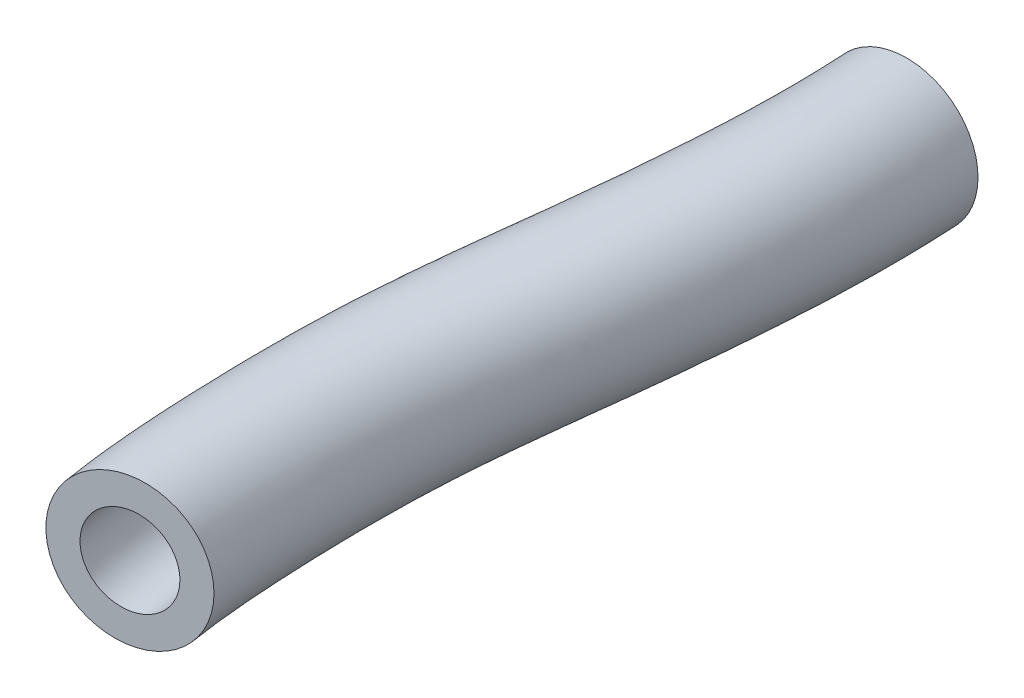
SolidWorks part; units mm, degrees
material "Rubber"
ref_plane "Front Plane" through (0, 0, 0) normal (0, 0, 1) x (1, 0, 0)
ref_plane "Top Plane" through (0, 0, 0) normal (0, 1, 0) x (1, 0, 0)
ref_plane "Right Plane" through (0, 0, 0) normal (1, 0, 0) x (0, 0, -1)
sketch3d "3DSketch1"
  line L0 (-0.2835, -1.1225, 176.7778) -> (-6.8913, -1.6732, 126.4124) construction
  circle A0 centre (0, 0, 24.058) radius 7.5 construction
  circle A1 centre (-6.8913, -1.6732, 126.4124) radius 9.525 construction
  spline S0 degree 3 poles (0, 0, 0) (0.9431, 0.1568, 13.8798) (-2.8576, -0.4693, 64.5894) (-9.8507, -1.7292, 81.5582) (-6.8802, -1.6984, 129.5265) (-5.3863, -1.5478, 137.8842) knots 0 0 0 0 0.211217 0.853755 1 1 1 1
  point P12 (0, 0, 31.558)
  point P15 (-5.6524, -1.5699, 135.8559)
sweep "Sweep1" add path "3DSketch1" circular profile diameter 26.924 parameters "D3"=26.924
sweep "Cut-Sweep1" cut path "3DSketch1<2>" circular profile diameter 16.002 parameters "D3"=16.002
sketch3d "3DSketch1<2>" same geometry as "3DSketch1"
